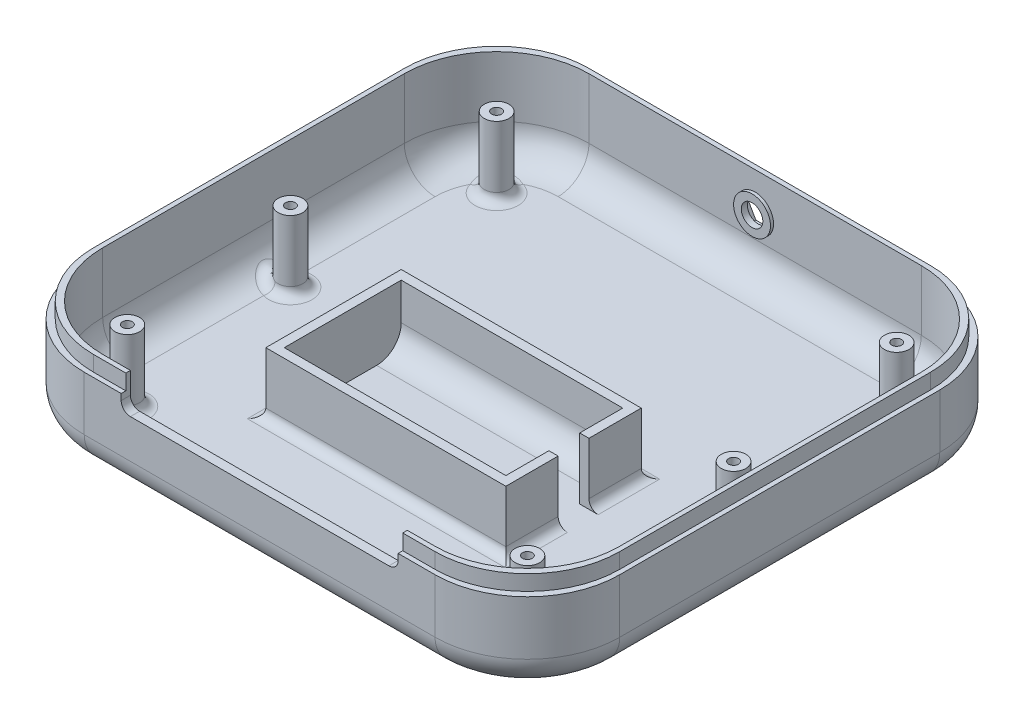
SolidWorks part; units mm, degrees
ref_plane "前视基准面" through (0, 0, 0) normal (0, 0, 1) x (1, 0, 0)
ref_plane "上视基准面" through (0, 0, 0) normal (0, 1, 0) x (1, 0, 0)
ref_plane "右视基准面" through (0, 0, 0) normal (1, 0, 0) x (0, 0, -1)
other "Configuration Table"
sketch "草图1" plane through (0, 0, 0) normal (0, 1, 0) x (1, 0, 0)
  line L1 (-87, -82) -> (87, -82)
  line L2 (-87, -82) -> (-87, 82)
  line L3 (-87, 82) -> (87, 82)
  line L4 (87, -82) -> (87, 82)
  line L5 (-87, -82) -> (87, 82) construction
  line L6 (-87, 82) -> (87, -82) construction
  point P0 (0, 0)
  dimension "D1" = 174
  dimension "D2" = 164
extrude "凸台-拉伸1" add sketch "草图1" along normal blind 3
sketch "草图2" plane through (0, 3, 0) normal (0, 1, 0) x (1, 0, 0)
  line L4 (87, -82) -> (87, 82)
  line L5 (87, 82) -> (-87, 82)
  line L6 (-87, 82) -> (-87, -82)
  line L7 (-87, -82) -> (87, -82)
  line L8 (87, -82) -> (87, 82)
  line L9 (87, 82) -> (-87, 82)
  line L10 (-87, 82) -> (-87, -82)
  line L11 (-87, -82) -> (87, -82)
  dimension "D1" = 0
extrude "拉伸-薄壁1" add sketch "草图2" along normal blind 24.6 thin thin type one direction reverse wall 3
sketch "草图3" plane through (0, 3, 0) normal (0, 1, 0) x (1, 0, 0)
  line L0 (0, -79) -> (0, 79) construction
  line L1 (-84, -79) -> (84, -79) construction
  line L2 (84, 79) -> (-84, 79) construction
  line L3 (84, -79) -> (84, 79) construction
  line L4 (84, 0) -> (-84, 0) construction
  line L5 (-84, 79) -> (-84, -79) construction
  line L6 (50, 75) -> (-50, 75)
  line L7 (-80, -45) -> (-80, 45)
  line L8 (80, -45) -> (80, 45)
  line L9 (50, -75) -> (-50, -75)
  arc A0 (-80, 45) -> (-50, 75) centre (-50, 45) cw
  arc A1 (80, 45) -> (50, 75) centre (50, 45) ccw
  arc A2 (80, -45) -> (50, -75) centre (50, -45) cw
  arc A3 (-80, -45) -> (-50, -75) centre (-50, -45) ccw
  circle A4 centre (-65, -60) radius 4
  circle A5 centre (65, -60) radius 4
  circle A6 centre (65, 60) radius 4
  circle A7 centre (-65, 60) radius 4
  circle A8 centre (-72, 0) radius 4
  circle A9 centre (72, 0) radius 4
  point P21 (-80, 0)
  point P22 (0, 75)
  point P28 (80, 0)
  point P32 (0, -19)
  dimension "D1" = 8
  dimension "D8" = 8
  dimension "D2" = 45
  dimension "D3" = 80
  dimension "D4" = 75
  dimension "D5" = 65
  dimension "D6" = 60
  dimension "D7" = 72
extrude "凸台-拉伸2" add sketch "草图3" along normal blind 23 contours A8 | A7 | A6 | A9 | A5 | A4
sketch "草图10" plane through (0, 27.6, 0) normal (0, 1, 0) x (1, 0, 0)
  line L0 (-84, -79) -> (84, -79) construction
  line L1 (84, -79) -> (84, 79) construction
  line L2 (84, 79) -> (-84, 79) construction
  line L3 (-84, 79) -> (-84, -79) construction
  line L4 (-84, -79) -> (84, -79)
  line L5 (84, -79) -> (84, 79)
  line L6 (84, 79) -> (-84, 79)
  line L7 (-84, 79) -> (-84, -79)
extrude "拉伸-薄壁3" add sketch "草图10" along normal blind 5 thin
sketch "草图13" plane through (0, 3, 0) normal (0, 1, 0) x (1, 0, 0)
  line L0 (0, -79) -> (0, 79) construction
  line L1 (-84, -79) -> (84, -79) construction
  line L2 (84, 79) -> (-84, 79) construction
  line L3 (-84, 0) -> (84, 0) construction
  line L4 (-84, 79) -> (-84, -79) construction
  line L5 (84, -79) -> (84, 79) construction
  line L7 (-36, -38) -> (36, -38)
  line L8 (-36, -38) -> (-36, 0)
  line L9 (-36, 0) -> (36, 0)
  line L10 (36, -38) -> (36, 0)
  line L11 (-36, -38) -> (36, 0) construction
  line L12 (-36, 0) -> (36, -38) construction
  point P12 (0, -19)
  dimension "D1" = 38
  dimension "D2" = 72
extrude "拉伸-薄壁5" add sketch "草图13" along normal blind 20 thin
sketch "草图14" plane through (39, 0, 0) normal (1, 0, 0) x (0, 0, -1)
  line L0 (-19, 3) -> (-19, 23) construction
  line L1 (-41, 3) -> (3, 3) construction
  line L2 (-41, 23) -> (3, 23) construction
  line L4 (-24, 3) -> (-14, 3)
  line L5 (-24, 3) -> (-24, 23)
  line L6 (-24, 23) -> (-14, 23)
  line L7 (-14, 3) -> (-14, 23)
  line L8 (-24, 3) -> (-14, 23) construction
  line L9 (-24, 23) -> (-14, 3) construction
  point P6 (-19, 13)
  dimension "D1" = 10
extrude "切除-拉伸3" cut sketch "草图14" against normal up to next
fillet "圆角20" radius 30 12 edges at (84, 17.8, 79) (84, 17.8, -79) (-84, 17.8, -79) (-84, 17.8, 79) (-85.5, 30.1, -80.5) (-85.5, 30.1, 80.5) (85.5, 30.1, 80.5) (85.5, 30.1, -80.5) (87, 13.8, 82) (-87, 13.8, 82) (-87, 13.8, -82) (87, 13.8, -82)
fillet "圆角21" radius 10 16 edges at (78.2132, 0, 73.2132) (0, 0, 82) (-78.2132, 0, 73.2132) (-87, 0, 0) (-78.2132, 0, -73.2132) (0, 0, -82) (78.2132, 0, -73.2132) (-75.2132, 3, -70.2132) (0, 3, -79) (75.2132, 3, -70.2132) (84, 3, 0) (75.2132, 3, 70.2132) (0, 3, 79) (-75.2132, 3, 70.2132) (87, 0, 0) (-84, 3, 0)
fillet "圆角23" radius 8 2 edges at (0, 3, 38) (0, 3, 0)
fillet "圆角24" radius 3 13 edges at (75.9966, 3.2014, 0.1645) (-75.9966, 3.2014, -0.1645) (39, 3, 5.5) (39, 3, 32.5) (0, 3, -3) (0, 3, 41) (-39, 3, 19) (65, 3, -64) (68, 3, 0) (65, 3, 56) (-65, 3, 56) (-65, 3, -64) (-68, 3, 0)
sketch "草图18" plane through (0, 0, -79) normal (0, 0, 1) x (1, 0, 0)
  line L0 (0, 27.6) -> (0, 13) construction
  line L3 (55.5, 27.6) -> (-55.5, 27.6) construction
  line L4 (55.5, 27.6) -> (-55.5, 27.6) construction
  line L5 (-54, 13) -> (54, 13) construction
  circle A0 centre (0, 20.3) radius 6
  point P5 (0, 20.3)
  dimension "D1" = 12
extrude "凸台-拉伸3" add sketch "草图18" along normal blind 1
sketch "草图19" plane through (0, 0, -78) normal (0, 0, 1) x (1, 0, 0)
  line L0 (0, 26.3) -> (0, 14.3) construction
  circle A0 centre (0, 20.3) radius 6 construction
  circle A1 centre (0, 20.3) radius 3.5
  dimension "D1" = 7
extrude "切除-拉伸7" cut sketch "草图19" against normal up to next
sketch "草图20" plane through (0, 0, -82) normal (0, 0, -1) x (-1, 0, 0)
  line L0 (0, 23.8) -> (0, 16.8) construction
  line L1 (-2.75, 25.0631) -> (2.75, 25.0631)
  line L2 (2.75, 25.0631) -> (5.5, 20.3)
  line L3 (5.5, 20.3) -> (2.75, 15.5369)
  line L4 (2.75, 15.5369) -> (-2.75, 15.5369)
  line L5 (-2.75, 15.5369) -> (-5.5, 20.3)
  line L6 (-5.5, 20.3) -> (-2.75, 25.0631)
  line L7 (-2.75, 25.0631) -> (2.75, 15.5369) construction
  line L8 (-2.75, 15.5369) -> (2.75, 25.0631) construction
  line L9 (5.5, 20.3) -> (-5.5, 20.3) construction
  circle A0 centre (0, 20.3) radius 3.5 construction
  point P7 (0, 20.3)
  point P12 (0, 20.3)
  dimension "D1" = 120
  dimension "D2" = 120
  dimension "D3" = 5.5
extrude "切除-拉伸8" cut sketch "草图20" against normal blind 2
sketch "草图22" plane through (0, 0, 82) normal (0, 0, 1) x (1, 0, 0)
  line L0 (0, 10) -> (0, 27.6) construction
  line L1 (-57, 10) -> (57, 10) construction
  line L2 (-57, 27.6) -> (57, 27.6) construction
  line L3 (-55.5, 32.6) -> (55.5, 32.6) construction
  line L4 (-45, 22.6) -> (45, 22.6)
  line L5 (-45, 22.6) -> (-45, 32.6)
  line L6 (-45, 32.6) -> (45, 32.6)
  line L7 (45, 22.6) -> (45, 32.6)
  line L8 (-45, 22.6) -> (45, 32.6) construction
  line L9 (-45, 32.6) -> (45, 22.6) construction
  dimension "D1" = 90
extrude "切除-拉伸9" cut sketch "草图22" against normal up to next
sketch "草图23" plane through (0, 26, 0) normal (0, 1, 0) x (1, 0, 0)
  line L0 (0, 69) -> (0, -69) construction
  line L1 (54, 69) -> (-54, 69) construction
  line L2 (-54, -69) -> (54, -69) construction
  line L3 (-84, 0) -> (84, 0) construction
  line L4 (-84, 49) -> (-84, -49) construction
  line L5 (84, -49) -> (84, 49) construction
  circle A0 centre (-65, 60) radius 1.6
  circle A1 centre (65, 60) radius 1.6
  circle A2 centre (65, -60) radius 1.6
  circle A3 centre (-65, -60) radius 1.6
  circle A4 centre (-72, 0) radius 1.6
  circle A5 centre (72, 0) radius 1.6
  dimension "D1" = 3.2
  dimension "D2" = 3.2
extrude "切除-拉伸10" cut sketch "草图23" against normal blind 10
fillet "圆角25" radius 3 2 edges at (45, 22.6, 80.5) (-45, 22.6, 80.5)
